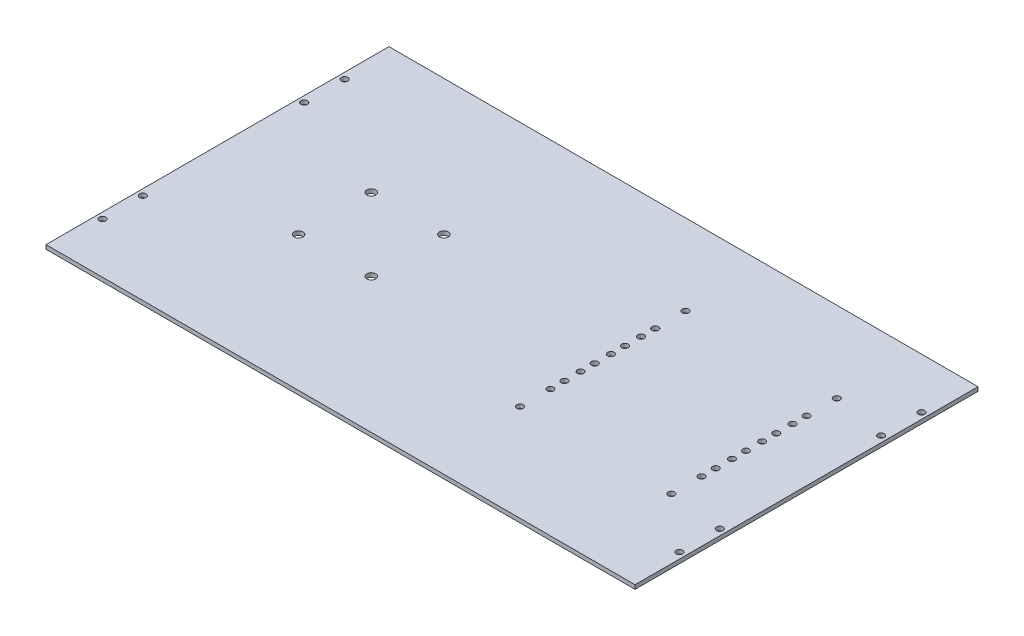
SolidWorks part; units mm, degrees
material "Thornel Mat VMA"
ref_plane "前视基准面" through (0, 0, 0) normal (0, 0, 1) x (1, 0, 0)
ref_plane "上视基准面" through (0, 0, 0) normal (0, 1, 0) x (1, 0, 0)
ref_plane "右视基准面" through (0, 0, 0) normal (1, 0, 0) x (0, 0, -1)
sketch "草图1" plane through (0, 0, 0) normal (0, 1, 0) x (1, 0, 0)
  line L0 (3, 45) -> (3, 25) construction
  line L1 (0, 0) -> (292, 0)
  line L2 (0, 0) -> (0, 170)
  line L3 (0, 170) -> (292, 170)
  line L4 (292, 0) -> (292, 170)
  line L5 (3, 145) -> (3, 125) construction
  line L7 (289, 45) -> (289, 25) construction
  line L8 (289, 145) -> (289, 125) construction
  line L9 (0, 85) -> (58.2249, 85) construction
  line L14 (58.2249, 103) -> (58.2249, 85) construction
  line L21 (58.2249, 103) -> (94.2249, 103) construction
  line L22 (58.2249, 67) -> (94.2249, 67) construction
  line L23 (94.2249, 67) -> (94.2249, 103) construction
  line L25 (58.2249, 85) -> (58.2249, 67) construction
  circle A0 centre (3, 145) radius 1.6
  circle A1 centre (3, 125) radius 1.6
  circle A2 centre (3, 45) radius 1.6
  circle A3 centre (3, 25) radius 1.6
  circle A4 centre (289, 25) radius 1.6
  circle A5 centre (289, 45) radius 1.6
  circle A6 centre (289, 125) radius 1.6
  circle A7 centre (289, 145) radius 1.6
  circle A8 centre (187, 130) radius 1.6
  circle A9 centre (262, 130) radius 1.6
  circle A10 centre (262, 108) radius 1.6
  circle A11 centre (187, 108) radius 1.6
  circle A12 centre (187, 115) radius 1.6
  circle A13 centre (262, 115) radius 1.6
  circle A14 centre (187, 93) radius 1.6
  circle A15 centre (262, 93) radius 1.6
  circle A16 centre (187, 100) radius 1.6
  circle A17 centre (262, 100) radius 1.6
  circle A18 centre (187, 78) radius 1.6
  circle A19 centre (262, 78) radius 1.6
  circle A20 centre (187, 85) radius 1.6
  circle A21 centre (262, 85) radius 1.6
  circle A22 centre (187, 63) radius 1.6
  circle A23 centre (262, 63) radius 1.6
  circle A24 centre (187, 70) radius 1.6
  circle A25 centre (262, 70) radius 1.6
  circle A26 centre (187, 48) radius 1.6
  circle A27 centre (262, 48) radius 1.6
  circle A28 centre (58.2249, 103) radius 2.2
  circle A29 centre (94.2249, 103) radius 2.2
  circle A30 centre (94.2249, 67) radius 2.2
  circle A31 centre (58.2249, 67) radius 2.2
  dimension "D3" = 20
  dimension "D5" = 3.2
  dimension "D7" = 25
  dimension "D14" = 3.2
  dimension "D9" = 18
  dimension "D1" = 292
  dimension "D2" = 170
  dimension "D4" = 3
  dimension "D6" = 25
  dimension "D8" = 20
  dimension "D10" = 18
  dimension "D11" = 36
  dimension "D12" = 22
  dimension "D13" = 75
  dimension "D19" = 36
  dimension "D17" = 5
extrude "凸台-拉伸1" add sketch "草图1" along normal blind 2
